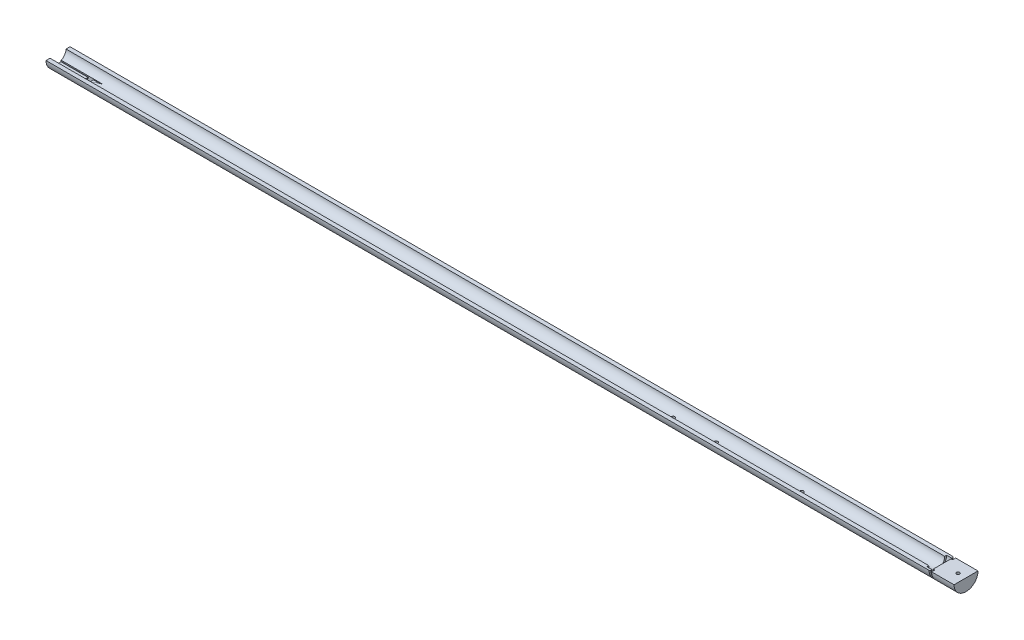
SolidWorks part; units mm, degrees
ref_plane "Front Plane" through (0, 0, 0) normal (0, 0, 1) x (1, 0, 0)
ref_plane "Top Plane" through (0, 0, 0) normal (0, 1, 0) x (1, 0, 0)
ref_plane "Right Plane" through (0, 0, 0) normal (1, 0, 0) x (0, 0, -1)
sketch "Sketch1" plane through (0, 0, 0) normal (0, 1, 0) x (1, 0, 0)
  line L1 (0, 0) -> (1803.4, 0)
  line L2 (0, 0) -> (0, 57.15)
  line L3 (0, 57.15) -> (1803.4, 57.15)
  line L4 (1803.4, 0) -> (1803.4, 57.15)
  dimension "blank_length" = 1803.4
  dimension "blank_width" = 57.15
extrude "wood block" add sketch "Sketch1" along normal blind 28.575
ref_plane "Plane1" through (0, 0, -28.575) normal (0, 0, 1) x (1, 0, 0)
sketch "Sketch2" plane through (0, 0, -28.575) normal (0, 0, 1) x (1, 0, 0)
  line L0 (1755.775, 28.575) -> (0, 28.575)
  line L2 (0, 12.7) -> (1755.775, 12.7)
  line L5 (0, 28.575) -> (0, 12.7)
  line L6 (0, 28.575) -> (0, 0) construction
  line L7 (1755.775, 28.575) -> (1755.775, 12.7)
  line L8 (0, 28.575) -> (1803.4, 28.575) construction
  point P0 (1755.775, 28.575)
  dimension "bore_inner_radius" = 15.875
  dimension "finished_length" = 1755.775
revolve "Inner Bore" cut sketch "Sketch2" angle 360 about L0
sketch "Sketch12" plane through (0, 0, -28.575) normal (0, 0, 1) x (1, 0, 0)
  line L0 (0, 28.575) -> (1803.4, 28.575) construction
  line L1 (1745.234, 28.575) -> (1755.775, 28.575)
  line L2 (1745.234, 28.575) -> (1745.234, 8.89)
  line L3 (1745.234, 8.89) -> (1755.775, 8.89)
  line L4 (1755.775, 28.575) -> (1755.775, 8.89)
  line L5 (0, 28.575) -> (0, 0) construction
  point P4 (1737.5044, 28.575)
  dimension "flange_depth" = 10.541
  dimension "finished_length" = 1755.775
  dimension "flange_OD" = 19.685
revolve "Cut-Revolve1" cut sketch "Sketch12" angle 360 about L1
ref_axis "Axis1" through (0, 28.575, -28.575) along (1, 0, 0)
sketch "Sketch5" plane through (0, 0, -28.575) normal (0, 0, 1) x (1, 0, 0)
  line L0 (53.975, 28.575) -> (53.975, 12.1285)
  line L3 (53.975, 0) -> (64.135, 0)
  line L4 (64.135, 0) -> (64.135, 12.1285) construction
  line L6 (64.135, 28.575) -> (53.975, 28.575)
  line L13 (64.135, 12.1285) -> (97.4578, 0)
  line L14 (97.4578, 0) -> (64.135, 0)
  line L15 (64.135, 12.1285) -> (64.135, 28.575)
  line L16 (53.975, 12.1285) -> (48.9512, 0)
  line L17 (48.9512, 0) -> (53.975, 0)
  line L18 (53.975, 12.1285) -> (53.975, 0) construction
  line L29 (0, 0) -> (1803.4, 0) construction
  line L34 (0, 28.575) -> (0, 0) construction
  line L35 (0, 28.575) -> (1803.4, 28.575) construction
  line L36 (0, 0) -> (1803.4, 0) construction
  line L37 (64.135, 12.1285) -> (53.975, 12.1285) construction
  point P2 (53.975, 28.575)
  point P3 (53.975, 12.7)
  point P4 (28.1259, -20.5033)
  point P6 (1755.775, 28.575)
  point P11 (0, 28.575)
  point P12 (1803.4, 28.575)
  point P21 (53.975, 28.575)
  point P22 (1771.65, 28.575)
  point P23 (1755.775, 28.575)
  point P24 (53.975, 28.575)
  point P25 (38.1, 28.575)
  point P26 (53.975, 28.575)
  point P27 (1755.775, 28.575)
  point P28 (0, 28.575)
  point P29 (0, 0)
  point P30 (1803.4, 28.575)
  point P31 (1803.4, 0)
  point P32 (1803.4, 28.575)
  point P33 (1803.4, 0)
  point P34 (0, 28.575)
  point P35 (0, 0)
  point P36 (1803.4, 28.575)
  point P37 (0, 28.575)
  point P38 (1803.4, 0)
  point P39 (0, 0)
  point P40 (0, 0)
  point P41 (1803.4, 0)
  point P42 (1755.775, 28.575)
  point P43 (1755.775, 12.7)
  point P46 (1755.775, 28.575)
  point P47 (53.975, 28.575)
  point P48 (1771.65, 28.575)
  point P49 (1755.775, 28.575)
  point P50 (53.975, 28.575)
  point P51 (38.1, 28.575)
  point P52 (53.975, 28.575)
  point P53 (1755.775, 28.575)
  dimension "fipple_gap" = 10.16
  dimension "fipple_ramp" = 20
  dimension "flue_depth" = 12.1285
  dimension "gap_beginning" = 53.975
  dimension "flue_dam" = 22.5
extrude "fipple" cut sketch "Sketch5" against normal mid plane 12.7
sketch "Sketch3" plane through (0, 28.575, 0) normal (0, 1, 0) x (1, 0, 0)
  line L122 (64.135, 34.925) -> (64.135, 22.225) construction
  line L123 (1476.629, 28.575) -> (1306.449, 28.575) construction
  line L124 (1306.449, 28.575) -> (1221.359, 28.575) construction
  line L125 (1221.359, 28.575) -> (64.135, 28.575) construction
  circle A0 centre (1476.629, 28.575) radius 3.81
  circle A1 centre (1306.449, 28.575) radius 3.81
  circle A2 centre (1221.359, 28.575) radius 3.81
  point P2 (-6.496, 28.575)
  point P3 (6.496, 28.575)
  point P10 (53.975, 22.225)
  point P11 (74.081, 22.225)
  point P12 (53.975, 34.925)
  point P13 (64.135, 34.925)
  point P14 (64.135, 34.925)
  point P15 (64.135, 22.225)
  point P16 (53.975, 22.225)
  point P17 (64.135, 22.225)
  point P18 (1724.025, 44.45)
  point P19 (53.975, 44.45)
  point P20 (1724.025, 28.575)
  point P21 (1724.025, 12.7)
  point P22 (1724.025, 44.45)
  point P23 (53.975, 28.575)
  point P24 (53.975, 44.45)
  point P25 (53.975, 12.7)
  point P26 (53.975, 12.7)
  point P27 (1724.025, 12.7)
  point P28 (1803.4, 4.7625)
  point P29 (1803.4, 52.3875)
  point P30 (0, 52.3875)
  point P31 (0, 4.7625)
  point P32 (53.975, 12.7)
  point P33 (53.975, 22.225)
  point P34 (53.975, 22.225)
  point P35 (53.975, 34.925)
  point P36 (53.975, 34.925)
  point P37 (53.975, 44.45)
  point P38 (1724.025, 12.7)
  point P39 (1724.025, 44.45)
  point P40 (64.135, 34.925)
  point P41 (64.135, 22.225)
  point P42 (74.081, 34.925)
  point P43 (64.135, 34.925)
  point P44 (74.081, 22.225)
  point P45 (64.135, 22.225)
  point P46 (1803.4, 4.7625)
  point P47 (0, 4.7625)
  point P48 (0, 52.3875)
  point P49 (1803.4, 52.3875)
  point P50 (53.975, 34.925)
  point P51 (74.081, 34.925)
  point P52 (74.081, 22.225)
  point P53 (74.081, 34.925)
  point P54 (-54.3985, 28.575)
  point P55 (76.4501, 28.575)
  point P56 (11.0258, 4.7625)
  point P57 (11.0258, 52.3875)
  point P58 (11.0258, 28.575)
  point P59 (53.975, 22.225)
  point P60 (53.975, 34.925)
  point P61 (1803.4, 4.7625)
  point P62 (1803.4, 52.3875)
  point P63 (0, 52.3875)
  point P64 (0, 4.7625)
  point P65 (0, 0)
  point P66 (1803.4, 0)
  point P67 (0, 0)
  point P68 (0, 57.15)
  point P69 (0, 57.15)
  point P70 (1803.4, 57.15)
  point P71 (1803.4, 0)
  point P72 (1803.4, 57.15)
  point P73 (1739.9, 28.575)
  point P74 (38.1, 28.575)
  point P75 (0, 28.575)
  point P76 (1803.4, 28.575)
  point P77 (53.975, 28.575)
  point P78 (1724.025, 28.575)
  point P79 (1803.4, 28.575)
  point P80 (0, 28.575)
  point P81 (53.975, 28.575)
  point P82 (64.135, 28.575)
  point P83 (64.135, 28.575)
  point P84 (53.975, 28.575)
  point P85 (0, 28.575)
  point P86 (1803.4, 28.575)
  point P87 (0, 28.575)
  point P88 (159.6887, 28.575)
  point P89 (0, 28.575)
  point P90 (159.6887, 28.575)
  point P91 (64.135, 28.575)
  point P92 (89.535, 28.575)
  point P93 (89.535, 28.575)
  point P94 (64.135, 28.575)
  point P95 (0, 57.15)
  point P96 (0, 0)
  point P97 (-13.0969, 0)
  point P98 (13.0969, 0)
  point P99 (0, -13.0969)
  point P100 (0, 13.0969)
  point P101 (53.975, 22.225)
  point P102 (74.081, 22.225)
  point P103 (53.975, 34.925)
  point P104 (64.135, 34.925)
  point P105 (64.135, 34.925)
  point P106 (64.135, 22.225)
  point P107 (53.975, 22.225)
  point P108 (64.135, 22.225)
  point P109 (1724.025, 44.45)
  point P110 (53.975, 44.45)
  point P111 (1724.025, 28.575)
  point P112 (1724.025, 12.7)
  point P113 (1724.025, 44.45)
  point P114 (53.975, 28.575)
  point P115 (53.975, 44.45)
  point P116 (53.975, 12.7)
  point P117 (53.975, 12.7)
  point P118 (1724.025, 12.7)
  point P119 (1803.4, 4.7625)
  point P120 (1803.4, 52.3875)
  point P121 (0, 52.3875)
  point P122 (0, 4.7625)
  point P123 (53.975, 12.7)
  point P124 (53.975, 22.225)
  point P125 (53.975, 22.225)
  point P126 (53.975, 34.925)
  point P127 (53.975, 34.925)
  point P128 (53.975, 44.45)
  point P129 (1724.025, 12.7)
  point P130 (1724.025, 44.45)
  point P131 (64.135, 34.925)
  point P132 (64.135, 22.225)
  point P133 (74.081, 34.925)
  point P134 (64.135, 34.925)
  point P135 (74.081, 22.225)
  point P136 (64.135, 22.225)
  point P137 (1803.4, 4.7625)
  point P138 (0, 4.7625)
  point P139 (0, 52.3875)
  point P140 (1803.4, 52.3875)
  point P141 (53.975, 34.925)
  point P142 (74.081, 34.925)
  point P143 (74.081, 22.225)
  point P144 (74.081, 34.925)
  point P145 (-54.3985, 28.575)
  point P146 (76.4501, 28.575)
  point P147 (11.0258, 4.7625)
  point P148 (11.0258, 52.3875)
  point P149 (11.0258, 28.575)
  point P150 (53.975, 22.225)
  point P151 (53.975, 34.925)
  point P152 (1803.4, 4.7625)
  point P153 (1803.4, 52.3875)
  point P154 (0, 52.3875)
  point P155 (0, 4.7625)
  point P156 (0, 0)
  point P157 (1803.4, 0)
  point P158 (0, 0)
  point P159 (0, 57.15)
  point P160 (0, 57.15)
  point P161 (1803.4, 57.15)
  point P162 (1803.4, 0)
  point P163 (1803.4, 57.15)
  point P164 (1739.9, 28.575)
  point P165 (38.1, 28.575)
  point P166 (0, 28.575)
  point P167 (1803.4, 28.575)
  point P168 (53.975, 28.575)
  point P169 (1724.025, 28.575)
  point P170 (1803.4, 28.575)
  point P171 (0, 28.575)
  point P172 (53.975, 28.575)
  point P173 (64.135, 28.575)
  point P174 (64.135, 28.575)
  point P175 (53.975, 28.575)
  point P176 (0, 28.575)
  point P177 (1803.4, 28.575)
  point P178 (0, 28.575)
  point P179 (159.6887, 28.575)
  point P180 (0, 28.575)
  point P181 (159.6887, 28.575)
  point P182 (64.135, 28.575)
  point P183 (89.535, 28.575)
  point P184 (89.535, 28.575)
  point P185 (64.135, 28.575)
  point P186 (0, 57.15)
  point P187 (0, 0)
  point P188 (-13.0969, 0)
  point P189 (13.0969, 0)
  point P190 (0, -13.0969)
  point P191 (0, 13.0969)
  point P192 (-6.496, 28.575)
  point P193 (6.496, 28.575)
  point P194 (53.975, 22.225)
  point P195 (74.081, 22.225)
  point P196 (53.975, 34.925)
  point P197 (64.135, 34.925)
  point P198 (64.135, 34.925)
  point P199 (64.135, 22.225)
  point P200 (53.975, 22.225)
  point P201 (64.135, 22.225)
  point P202 (1724.025, 44.45)
  point P203 (53.975, 44.45)
  point P204 (1724.025, 28.575)
  point P205 (1724.025, 12.7)
  point P206 (1724.025, 44.45)
  point P207 (53.975, 28.575)
  point P208 (53.975, 44.45)
  point P209 (53.975, 12.7)
  point P210 (53.975, 12.7)
  point P211 (1724.025, 12.7)
  point P212 (1803.4, 4.7625)
  point P213 (1803.4, 52.3875)
  point P214 (0, 52.3875)
  point P215 (0, 4.7625)
  point P216 (53.975, 12.7)
  point P217 (53.975, 22.225)
  point P218 (53.975, 22.225)
  point P219 (53.975, 34.925)
  point P220 (53.975, 34.925)
  point P221 (53.975, 44.45)
  point P222 (1724.025, 12.7)
  point P223 (1724.025, 44.45)
  point P224 (64.135, 34.925)
  point P225 (64.135, 22.225)
  point P226 (74.081, 34.925)
  point P227 (64.135, 34.925)
  point P228 (74.081, 22.225)
  point P229 (64.135, 22.225)
  point P230 (1803.4, 4.7625)
  point P231 (0, 4.7625)
  point P232 (0, 52.3875)
  point P233 (1803.4, 52.3875)
  point P234 (53.975, 34.925)
  point P235 (74.081, 34.925)
  point P236 (74.081, 22.225)
  point P237 (74.081, 34.925)
  point P238 (-54.3985, 28.575)
  point P239 (76.4501, 28.575)
  point P240 (11.0258, 4.7625)
  point P241 (11.0258, 52.3875)
  point P242 (11.0258, 28.575)
  point P243 (53.975, 22.225)
  point P244 (53.975, 34.925)
  point P245 (1803.4, 4.7625)
  point P246 (1803.4, 52.3875)
  point P247 (0, 52.3875)
  point P248 (0, 4.7625)
  point P249 (0, 0)
  point P250 (1803.4, 0)
  point P251 (0, 0)
  point P252 (0, 57.15)
  point P253 (0, 57.15)
  point P254 (1803.4, 57.15)
  point P255 (1803.4, 0)
  point P256 (1803.4, 57.15)
  point P257 (1739.9, 28.575)
  point P258 (38.1, 28.575)
  point P259 (0, 28.575)
  point P260 (1803.4, 28.575)
  point P261 (53.975, 28.575)
  point P262 (1724.025, 28.575)
  point P263 (1803.4, 28.575)
  point P264 (0, 28.575)
  point P265 (53.975, 28.575)
  point P266 (64.135, 28.575)
  point P267 (64.135, 28.575)
  point P268 (53.975, 28.575)
  point P269 (0, 28.575)
  point P270 (1803.4, 28.575)
  point P271 (0, 28.575)
  point P272 (159.6887, 28.575)
  point P273 (0, 28.575)
  point P274 (159.6887, 28.575)
  point P275 (64.135, 28.575)
  point P276 (89.535, 28.575)
  point P277 (89.535, 28.575)
  point P278 (64.135, 28.575)
  point P279 (0, 57.15)
  point P280 (0, 0)
  point P281 (-13.0969, 0)
  point P282 (13.0969, 0)
  point P283 (0, -13.0969)
  point P284 (0, 13.0969)
  point P285 (-6.496, 28.575)
  point P286 (6.496, 28.575)
  dimension "hole3_diameter" = 7.62
  dimension "hole2_diameter" = 7.62
  dimension "hole1_diameter" = 7.62
  dimension "fipple_to_hole1" = 1157.224
  dimension "fipple_to_hole2" = 1242.314
  dimension "fipple_to_hole3" = 1412.494
extrude "finger holes" cut sketch "Sketch3" against normal blind 25.4
sketch "Sketch9" plane through (0, 0, -28.575) normal (0, 0, 1) x (1, 0, 0)
  line L0 (64.135, 12.3825) -> (84.3737, 14.1532)
  line L1 (64.135, 12.1285) -> (64.135, 14.0253) construction
  line L2 (84.3737, 14.1532) -> (64.135, 16.8013)
  line L3 (64.135, 16.8013) -> (64.135, 12.3825)
  line L4 (1803.4, 28.575) -> (0, 28.575) construction
  dimension "fipple_height" = 0.254
  dimension "fipple_ramp_in" = 5
extrude "fipple inside chamfer" cut sketch "Sketch9" against normal up to vertex (6.35 mm away) and the other way up to vertex (6.35 mm away) up to point (53.975, 14.0253, -34.925) other way up to point (53.975, 14.0253, -22.225)
sketch "Sketch8" plane through (0, 0, 0) normal (-1, 0, 0) x (0, 0, 1)
  line L0 (-28.575, 28.575) -> (-28.575, 20.035) construction
  line L2 (-34.925, 14.0253) -> (-34.925, 12.1285) construction
  line L3 (-22.225, 28.575) -> (-34.925, 28.575)
  line L4 (-22.225, 28.575) -> (-22.225, 11.4951)
  line L5 (-22.225, 11.4951) -> (-34.925, 11.4951)
  line L6 (-34.925, 28.575) -> (-34.925, 11.4951)
  line L7 (-22.225, 28.575) -> (-34.925, 11.4951) construction
  line L8 (-22.225, 11.4951) -> (-34.925, 28.575) construction
  line L9 (-8.89, 28.575) -> (-48.26, 28.575) construction
  line L10 (-22.225, 12.3333) -> (-34.925, 12.3333) construction
  point P2 (-28.575, 28.575)
  point P13 (-22.225, 28.575)
  dimension "flue_depth" = 0.8382
extrude "flue" cut sketch "Sketch8" against normal up to next
fillet "Fillet1" radius 0.381 8 edges at (73.5238, 13.2039, -22.225) (73.5238, 13.2039, -34.925) (26.8563, 11.4951, -34.925) (26.8563, 11.4951, -22.225) (51.3319, 5.7475, -34.925) (51.3319, 5.7475, -22.225) (80.7964, 6.0643, -22.225) (80.7964, 6.0643, -34.925)
sketch "Sketch10" plane through (0, 28.575, 0) normal (0, 1, 0) x (1, 0, 0)
  line L0 (1803.4, 28.575) -> (1787.525, 28.575) construction
  line L1 (1803.4, 0) -> (1803.4, 57.15) construction
  circle A2 centre (1787.525, 28.575) radius 3.175
  dimension "dowel_pin_diameter" = 6.35
  dimension "dowel_pin_location" = 15.875
extrude "dowel pin hole" cut sketch "Sketch10" against normal blind 15.24
chamfer "Chamfer1" distance 16.7386 angle 45 2 edges at (901.7, 0, 0) (901.7, 0, -57.15)
sketch "Sketch6" plane through (0, 0, 0) normal (-1, 0, 0) x (0, 0, 1)
  line L0 (-8.89, 28.575) -> (-48.26, 28.575) construction
  circle A0 centre (-28.575, 28.575) radius 23.8125
  point P2 (-28.575, 28.575)
  point P3 (-28.575, 28.575)
  dimension "outer_diameter" = 47.625
extrude "outside diameter" cut sketch "Sketch6" against normal through all flip side to cut
sketch "Sketch11" plane through (0, 28.575, 0) normal (0, 1, 0) x (1, 0, 0)
  line L0 (1755.775, 4.7625) -> (1755.775, 12.7) construction
  line L1 (1803.4, 4.7625) -> (0, 4.7625) construction
  line L2 (1803.4, 4.7625) -> (1803.4, 52.3875) construction
  line L3 (1755.775, 4.7625) -> (1758.95, 4.7625)
  line L4 (1755.775, 4.7625) -> (1755.775, 11.1125)
  line L5 (1755.775, 11.1125) -> (1758.95, 11.1125)
  line L6 (1758.95, 4.7625) -> (1758.95, 11.1125)
  line L7 (0, 52.3875) -> (0, 44.45) construction
  dimension "groove_width" = 3.175
  dimension "groove_depth" = 6.35
  dimension "groove_location" = 47.625
  dimension "finished_length" = 1755.775
revolve "end length locator" cut sketch "Sketch11" angle 360 about axis through (0, 28.575, -28.575) along (1, 0, 0)
chamfer "chamfer at foot" distance 1.905 angle 45 1 edges at (1755.775, 4.7625, -28.575)
equation "\"g_body_OD\"= 47.625mm"
equation "\"g_body_ID\"= 31.75mm"
equation "\"g_body_L_finished\"= 1755.775mm"
equation "\"g_body_L_blank\"= 1803.4mm"
equation "\"g_body_blank_W\"= 57.15mm"
equation "\"g_dowel_OD\"= 6.35mm"
equation "\"g_thru_passage_OD\"= 12.7mm"
equation "\"g_glue_glap\"= 0.0762mm"
equation "\"c_dowel_clearance\"= 0mm"
equation "\"thickness@wood block\"= \"g_body_blank_W\" / 2"
equation "\"blank_length@Sketch1\"= \"g_body_L_blank\""
equation "\"blank_width@Sketch1\"= \"g_body_blank_W\""
equation "\"bore_inner_radius@Sketch2\"= \"g_body_ID\" / 2"
equation "\"outer_diameter@Sketch6\"= \"g_body_OD\""
equation "\"finished_length@Sketch11\"= \"g_body_L_finished\""
equation "\"dowel_pin_diameter@Sketch10\"= \"g_dowel_OD\" + \"c_dowel_clearance\""
